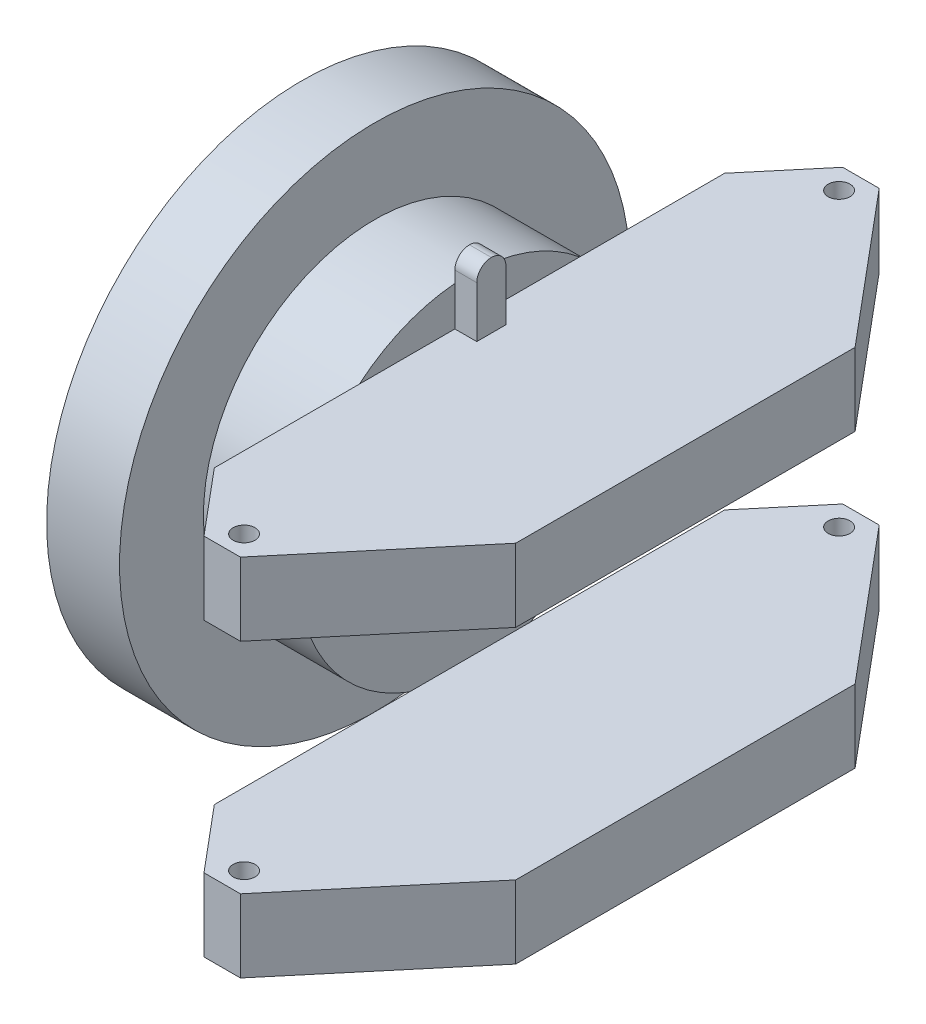
SolidWorks part; units mm, degrees
ref_plane "Front Plane" through (0, 0, 0) normal (0, 0, 1) x (1, 0, 0)
ref_plane "Top Plane" through (0, 0, 0) normal (0, 1, 0) x (1, 0, 0)
ref_plane "Right Plane" through (0, 0, 0) normal (1, 0, 0) x (0, 0, -1)
sketch "Sketch1" plane through (0, 0, 0) normal (1, 0, 0) x (0, 0, -1)
  circle A0 centre (0, 0) radius 35
  dimension "D1" = 70
extrude "Boss-Extrude1" add sketch "Sketch1" along normal blind 10
sketch "Sketch2" plane through (10, 0, 0) normal (1, 0, 0) x (0, 0, -1)
  circle A0 centre (0, 0) radius 23.5
  dimension "D1" = 47
extrude "Boss-Extrude2" add sketch "Sketch2" along normal blind 13
ref_plane "Plane1" through (0, 13, 0) normal (0, 1, 0) x (1, 0, 0)
sketch "Sketch4" plane through (0, 13, 0) normal (0, 1, 0) x (1, 0, 0)
  line L0 (23, 35) -> (23, -35)
  line L1 (23, -23.5) -> (23, 23.5) construction
  line L2 (23, -35) -> (30.3921, -43.8095)
  line L3 (30.3921, -43.8095) -> (35.3921, -43.8095)
  line L4 (35.3921, -43.8095) -> (52.6219, -23.2758)
  line L5 (35.3921, -43.8095) -> (41.9349, -43.8095) construction
  line L6 (52.6219, 23.2758) -> (52.6219, -23.2758)
  line L8 (23, 0) -> (71.9804, 0) construction
  line L9 (23, 35) -> (51.1049, 35) construction
  line L10 (23, 35) -> (30.3921, 43.8095)
  line L12 (35.3921, 43.8095) -> (52.6219, 23.2758)
  line L13 (30.3921, 43.8095) -> (35.3921, 43.8095)
  line L14 (23, -23.2758) -> (52.6219, -23.2758) construction
  dimension "D1" = 35
  dimension "D2" = 11.5
  dimension "D3" = 40
  dimension "D4" = 5
  dimension "D5" = 50
extrude "Boss-Extrude3" add sketch "Sketch4" along normal mid plane 10
sketch "Sketch5" plane through (0, 18, 0) normal (0, 1, 0) x (1, 0, 0)
  line L0 (32.8921, -43.8095) -> (32.8921, -40.8095) construction
  line L1 (30.3921, -43.8095) -> (35.3921, -43.8095) construction
  circle A0 centre (32.8921, -40.8095) radius 1.5
  dimension "D1" = 3
  dimension "D2" = 3
extrude "Cut-Extrude1" cut sketch "Sketch5" against normal through all
mirror "Mirror1" about plane through (0, 0, 0) normal (0, 0, 1) of "Cut-Extrude1"
sketch "Sketch6" plane through (10, 0, 0) normal (1, 0, 0) x (0, 0, -1)
  point P6 (0, 20.25)
sketch "Sketch9" plane through (23, 0, 0) normal (1, 0, 0) x (0, 0, -1)
  line L0 (0, 27) -> (0, 18) construction
  line L2 (15.1079, 18) -> (-15.1079, 18) construction
  line L4 (-2, 27) -> (2, 27)
  line L5 (-2, 27) -> (-2, 18)
  line L6 (-2, 18) -> (2, 18)
  line L7 (2, 27) -> (2, 18)
  line L8 (-2, 27) -> (2, 18) construction
  line L9 (-2, 18) -> (2, 27) construction
  point P4 (0, 22.5)
  dimension "D1" = 9
  dimension "D2" = 2
extrude "Boss-Extrude8" add sketch "Sketch9" along normal blind 3
fillet "Fillet3" radius 2 2 edges at (24.5, 27, -2) (24.5, 27, 2)
sketch "Sketch11" plane through (0, 0, 0) normal (-1, 0, 0) x (0, 0, 1)
  circle A0 centre (0, 0) radius 10
  dimension "D1" = 20
extrude "Cut-Extrude2" cut sketch "Sketch11" against normal blind 10
ref_plane "Plane3" through (0, -7, 0) normal (0, -1, 0) x (-1, 0, 0)
mirror "Mirror2" about plane through (0, -7, 0) normal (0, -1, 0) of "Cut-Extrude1", "Mirror1", "Boss-Extrude8", "Boss-Extrude3", "Fillet3"
